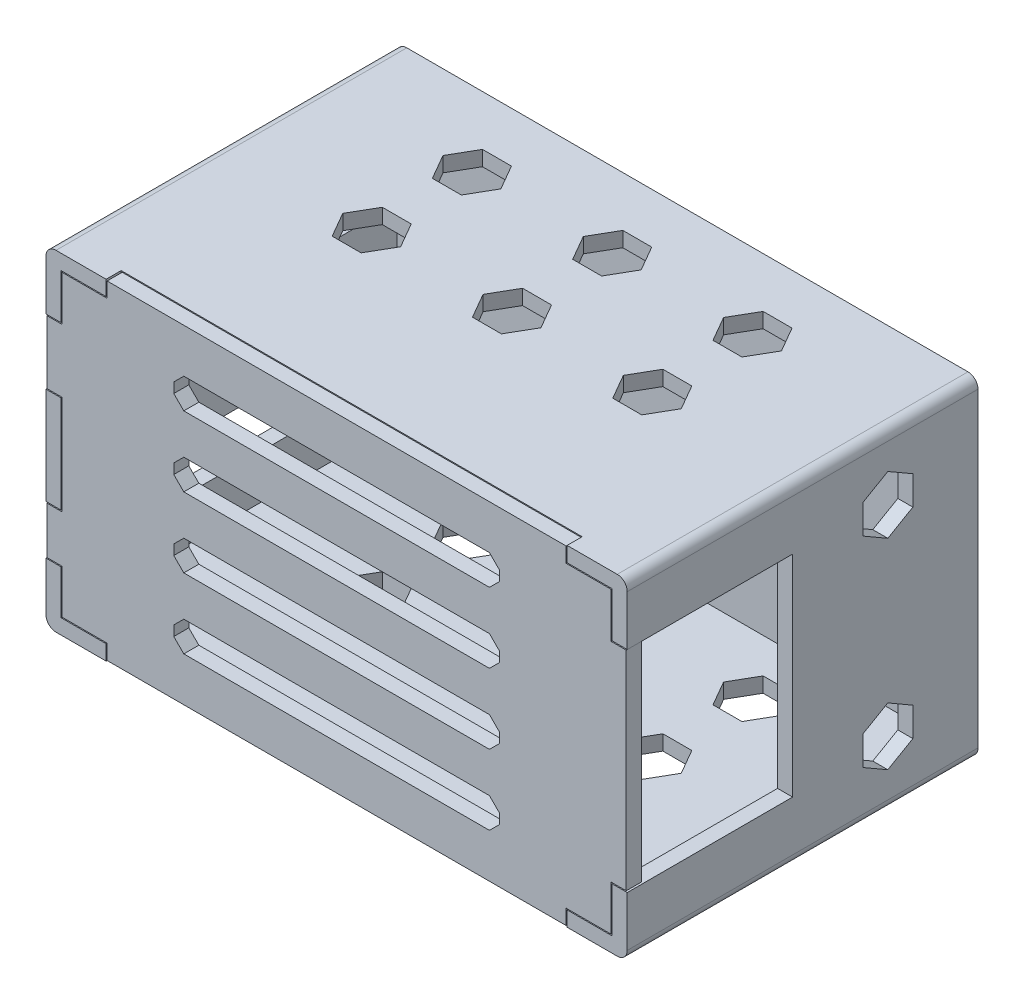
SolidWorks part; units mm, degrees
ref_plane "Front Plane" through (0, 0, 0) normal (0, 0, 1) x (1, 0, 0)
ref_plane "Top Plane" through (0, 0, 0) normal (0, 1, 0) x (1, 0, 0)
ref_plane "Right Plane" through (0, 0, 0) normal (1, 0, 0) x (0, 0, -1)
sketch "Sketch1" plane through (0, 0, 0) normal (0, 0, 1) x (1, 0, 0)
  line L0 (-58, -33) -> (-58, 33)
  line L1 (-55, -30) -> (55, -30)
  line L2 (-55, -30) -> (-55, 30)
  line L3 (-55, 30) -> (55, 30)
  line L4 (55, -30) -> (55, 30)
  line L5 (-55, -30) -> (55, 30) construction
  line L6 (-55, 30) -> (55, -30) construction
  line L7 (-58, 33) -> (58, 33)
  line L8 (58, -33) -> (58, 33)
  line L9 (-58, -33) -> (58, -33)
  point P0 (0, 0)
  dimension "D1" = 60
  dimension "125" = 110
  dimension "D3" = 3
extrude "Boss-Extrude1" add sketch "Sketch1" along normal blind 70
extrude "Boss-Extrude2" add sketch "Sketch1<2>" along normal blind 3 contours L1 L4 L3 L2 region at (0, 0, 0)
sketch "Sketch1<2>" plane through (0, 0, 0) normal (0, 0, 1) x (1, 0, 0) same geometry as "Sketch1"
sketch "Sketch2" plane through (-58, 0, 0) normal (-1, 0, 0) x (0, 0, 1)
  line L0 (70, 33) -> (70, -33) construction
  line L1 (70, -11.4) -> (5, -11.4)
  line L2 (70, -11.4) -> (70, -21.2)
  line L3 (70, -21.2) -> (5, -21.2)
  line L4 (5, -11.4) -> (5, -21.2)
  line L5 (0, 33) -> (0, -33) construction
  line L6 (70, 21) -> (5, 21)
  line L7 (70, 21) -> (70, 8)
  line L8 (70, 8) -> (5, 8)
  line L9 (5, 21) -> (5, 8)
  line L11 (70, 33) -> (0, 33) construction
  dimension "D1" = 5
  dimension "D2" = 13
  dimension "D3" = 9.8
  dimension "D4" = 19.4
  dimension "D5" = 12
extrude "Cut-Extrude1" cut sketch "Sketch2" against normal up to next
sketch "Sketch3" plane through (0, -33, 0) normal (0, -1, 0) x (1, 0, 0)
  line L0 (-58, 35) -> (58, 35) construction
  line L1 (-58, 70) -> (-58, 0) construction
  line L2 (58, 70) -> (58, 0) construction
  line L3 (-58, 15) -> (58, 15) construction
  line L9 (-25.1132, 40) -> (-30.8868, 40)
  line L14 (-30.8868, 40) -> (-33.7735, 35)
  line L15 (-33.7735, 35) -> (-30.8868, 30)
  line L20 (-30.8868, 30) -> (-25.1132, 30)
  line L21 (-25.1132, 30) -> (-22.2265, 35)
  line L22 (-58, 0) -> (58, 0) construction
  line L27 (-22.2265, 35) -> (-25.1132, 40)
  line L28 (2.8868, 40) -> (-2.8868, 40)
  line L33 (-2.8868, 40) -> (-5.7735, 35)
  line L34 (-5.7735, 35) -> (-2.8868, 30)
  line L39 (-2.8868, 30) -> (2.8868, 30)
  line L40 (2.8868, 30) -> (5.7735, 35)
  line L41 (5.7735, 35) -> (2.8868, 40)
  line L42 (30.8868, 40) -> (25.1132, 40)
  line L43 (25.1132, 40) -> (22.2265, 35)
  line L44 (22.2265, 35) -> (25.1132, 30)
  line L45 (25.1132, 30) -> (30.8868, 30)
  line L46 (30.8868, 30) -> (33.7735, 35)
  line L47 (33.7735, 35) -> (30.8868, 40)
  line L48 (30.8868, 20) -> (25.1132, 20)
  line L49 (25.1132, 20) -> (22.2265, 15)
  line L50 (22.2265, 15) -> (25.1132, 10)
  line L51 (25.1132, 10) -> (30.8868, 10)
  line L52 (30.8868, 10) -> (33.7735, 15)
  line L53 (33.7735, 15) -> (30.8868, 20)
  line L54 (2.8868, 20) -> (-2.8868, 20)
  line L55 (-2.8868, 20) -> (-5.7735, 15)
  line L56 (-5.7735, 15) -> (-2.8868, 10)
  line L57 (-2.8868, 10) -> (2.8868, 10)
  line L58 (2.8868, 10) -> (5.7735, 15)
  line L59 (5.7735, 15) -> (2.8868, 20)
  line L60 (-25.1132, 20) -> (-30.8868, 20)
  line L61 (-30.8868, 20) -> (-33.7735, 15)
  line L62 (-33.7735, 15) -> (-30.8868, 10)
  line L63 (-30.8868, 10) -> (-25.1132, 10)
  line L64 (-25.1132, 10) -> (-22.2265, 15)
  line L65 (-22.2265, 15) -> (-25.1132, 20)
  circle A0 centre (-28, 35) radius 5 construction
  circle A1 centre (0, 35) radius 5 construction
  circle A2 centre (28, 35) radius 5 construction
  circle A3 centre (28, 15) radius 5 construction
  circle A4 centre (0, 15) radius 5 construction
  circle A5 centre (-28, 15) radius 5 construction
  point P6 (-28, 35)
  point P11 (0, 35)
  point P16 (28, 35)
  point P23 (-28, 15)
  point P28 (0, 15)
  point P33 (28, 15)
  dimension "D5" = 10
  dimension "D1" = 28
  dimension "D2" = 28
  dimension "D3" = 15
  dimension "D4" = 20
extrude "Cut-Extrude2" cut sketch "Sketch3" against normal through all
sketch "Sketch4" plane through (58, 0, 0) normal (1, 0, 0) x (0, 0, -1)
  line L0 (-35, 33) -> (-35, -33) construction
  line L1 (-70, 33) -> (0, 33) construction
  line L2 (-40, -33) -> (-30, -33) construction
  line L3 (-18, 33) -> (-18, -33) construction
  line L4 (-20, -33) -> (-10, -33) construction
  line L5 (0, -33) -> (0, 33) construction
  line L7 (-40.7735, 20) -> (-37.8868, 15) construction
  line L8 (-37.8868, 15) -> (-32.1132, 15) construction
  line L9 (-32.1132, 15) -> (-29.2265, 20) construction
  line L10 (-29.2265, 20) -> (-32.1132, 25) construction
  line L11 (-32.1132, 25) -> (-37.8868, 25) construction
  line L12 (-37.8868, 25) -> (-40.7735, 20) construction
  line L13 (-18, 25.7735) -> (-23, 22.8868)
  line L14 (-23, 22.8868) -> (-23, 17.1132)
  line L15 (-23, 17.1132) -> (-18, 14.2265)
  line L16 (-18, 14.2265) -> (-13, 17.1132)
  line L17 (-13, 17.1132) -> (-13, 22.8868)
  line L18 (-13, 22.8868) -> (-18, 25.7735)
  line L19 (-18, -14.2265) -> (-23, -17.1132)
  line L20 (-23, -17.1132) -> (-23, -22.8868)
  line L21 (-23, -22.8868) -> (-18, -25.7735)
  line L22 (-18, -25.7735) -> (-13, -22.8868)
  line L23 (-13, -22.8868) -> (-13, -17.1132)
  line L24 (-13, -17.1132) -> (-18, -14.2265)
  line L25 (-40.7735, -20) -> (-37.8868, -25) construction
  line L26 (-37.8868, -25) -> (-32.1132, -25) construction
  line L27 (-32.1132, -25) -> (-29.2265, -20) construction
  line L28 (-29.2265, -20) -> (-32.1132, -15) construction
  line L29 (-32.1132, -15) -> (-37.8868, -15) construction
  line L30 (-37.8868, -15) -> (-40.7735, -20) construction
  circle A0 centre (-35, 20) radius 5 construction
  circle A1 centre (-18, 20) radius 5 construction
  circle A2 centre (-18, -20) radius 5 construction
  circle A3 centre (-35, -20) radius 5 construction
  dimension "D3" = 10
  dimension "D1" = 18
  dimension "D2" = 35
  dimension "D4" = 20
  dimension "D5" = 20
extrude "Cut-Extrude3" cut sketch "Sketch4" against normal up to next
sketch "Sketch5" plane through (0, 0, 70) normal (0, 0, 1) x (1, 0, 0)
  line L0 (58, 33) -> (-58, 33) construction
  line L1 (-46, 33) -> (46, 33)
  line L2 (-46, 33) -> (-46, 30)
  line L3 (-46, 30) -> (46, 30)
  line L4 (46, 33) -> (46, 30)
  line L5 (-55, 30) -> (55, 30) construction
  line L6 (58, -33) -> (58, 33) construction
  line L7 (-58, 33) -> (-58, 21) construction
  line L8 (-55, -30) -> (55, -30) construction
  line L9 (-46, -30) -> (46, -30)
  line L10 (-46, -30) -> (-46, -33)
  line L11 (-46, -33) -> (46, -33)
  line L12 (46, -30) -> (46, -33)
  line L13 (-58, -33) -> (58, -33) construction
  line L14 (-58, -21.2) -> (-58, -33) construction
  line L15 (55, -30) -> (55, 30) construction
  line L16 (55, 21) -> (58, 21)
  line L17 (55, 21) -> (55, -21)
  line L18 (55, -21) -> (58, -21)
  line L19 (58, 21) -> (58, -21)
  point P28 (55, 0)
  dimension "D1" = 12
  dimension "D2" = 12
  dimension "D3" = 12
  dimension "D4" = 12
  dimension "D5" = 12
extrude "Cut-Extrude4" cut sketch "Sketch5" against normal blind 3
sketch "Sketch6" plane through (0, 0, 67) normal (0, 0, 1) x (1, 0, 0)
  line L0 (-55, 21) -> (-58, 21) construction
  line L1 (-58, 21) -> (-58, 8) construction
  line L2 (-58, 8) -> (-55, 8) construction
  line L4 (-55, -11.4) -> (-58, -11.4) construction
  line L5 (-58, -11.4) -> (-58, -21.2) construction
  line L6 (-58, -21.2) -> (-55, -21.2) construction
  line L8 (-46, -30) -> (-46, -33) construction
  line L9 (-46, -33) -> (46, -33) construction
  line L10 (46, -33) -> (46, -30) construction
  line L13 (55, -21) -> (58, -21) construction
  line L14 (58, -21) -> (58, 21) construction
  line L15 (58, 21) -> (55, 21) construction
  line L16 (-46, 33) -> (-46, 30) construction
  line L18 (46, 30) -> (46, 33) construction
  line L19 (46, 33) -> (-46, 33) construction
  line L20 (-55, -30) -> (55, -30) construction
  line L21 (55, -30) -> (55, 30) construction
  line L22 (55, 30) -> (-55, 30) construction
  line L23 (-55, 30) -> (-55, -30) construction
  line L24 (-55, 21) -> (-58, 21)
  line L25 (-58, 21) -> (-58, 8)
  line L26 (-58, 8) -> (-55, 8)
  line L28 (-55, -11.4) -> (-58, -11.4)
  line L29 (-58, -11.4) -> (-58, -21.2)
  line L30 (-58, -21.2) -> (-55, -21.2)
  line L32 (-46, -30) -> (-46, -33)
  line L33 (-46, -33) -> (46, -33)
  line L34 (46, -33) -> (46, -30)
  line L37 (55, -21) -> (58, -21)
  line L38 (58, -21) -> (58, 21)
  line L39 (58, 21) -> (55, 21)
  line L40 (-46, 33) -> (-46, 30)
  line L42 (46, 30) -> (46, 33)
  line L43 (46, 33) -> (-46, 33)
  line L44 (-55, -30) -> (-46, -30)
  line L45 (55, -30) -> (55, -21)
  line L46 (55, 30) -> (46, 30)
  line L47 (-55, 30) -> (-55, 21)
  line L48 (-55, 8) -> (-55, -11.4)
  line L49 (-55, -21.2) -> (-55, -30)
  line L50 (46, -30) -> (55, -30)
  line L51 (55, 21) -> (55, 30)
  line L52 (-46, 30) -> (-55, 30)
  line L53 (54.8, 29.8) -> (45.8, 29.8)
  line L54 (45.8, 29.8) -> (45.8, 32.8)
  line L55 (45.8, 32.8) -> (-45.8, 32.8)
  line L56 (-45.8, 32.8) -> (-45.8, 29.8)
  line L57 (-45.8, 29.8) -> (-54.8, 29.8)
  line L58 (-54.8, 29.8) -> (-54.8, 20.8)
  line L59 (-54.8, 20.8) -> (-57.8, 20.8)
  line L60 (-57.8, 20.8) -> (-57.8, 8.2)
  line L61 (-57.8, 8.2) -> (-54.8, 8.2)
  line L62 (-54.8, 8.2) -> (-54.8, -11.6)
  line L63 (-54.8, -11.6) -> (-57.8, -11.6)
  line L64 (-57.8, -11.6) -> (-57.8, -21)
  line L65 (-57.8, -21) -> (-54.8, -21)
  line L66 (-54.8, -21) -> (-54.8, -29.8)
  line L67 (-54.8, -29.8) -> (-45.8, -29.8)
  line L68 (-45.8, -29.8) -> (-45.8, -32.8)
  line L69 (-45.8, -32.8) -> (45.8, -32.8)
  line L70 (45.8, -32.8) -> (45.8, -29.8)
  line L71 (45.8, -29.8) -> (54.8, -29.8)
  line L72 (54.8, -29.8) -> (54.8, -20.8)
  line L73 (54.8, -20.8) -> (57.8, -20.8)
  line L74 (57.8, -20.8) -> (57.8, 20.8)
  line L75 (57.8, 20.8) -> (54.8, 20.8)
  line L76 (54.8, 20.8) -> (54.8, 29.8)
  line M51 (55, 21) -> (55, -21)
  dimension "D1" = 0.2
extrude "Boss-Extrude3" add sketch "Sketch6" along normal blind 3 separate body contours L75 L76 L53 L54 L55 L56 L57 L58 L59 L60 L61 L62 L63 L64 L65 L66 L67 L68 L69 L70 L71 L72 L73 M51 | L74 L75 L73 M51 region at (-0.4554, 0.0124, 67) region at (56.4, 0, 67)
sketch "Sketch7" plane through (0, 0, 70) normal (0, 0, 1) x (1, 0, 0)
  line L1 (-32.5, 24) -> (32.5, 24)
  line L2 (-32.5, 24) -> (-32.5, 18)
  line L3 (-32.5, 18) -> (32.5, 18)
  line L4 (32.5, 24) -> (32.5, 18)
  line L5 (-32.5, 10) -> (32.5, 10)
  line L6 (-32.5, 10) -> (-32.5, 4)
  line L7 (-32.5, 4) -> (32.5, 4)
  line L8 (32.5, 10) -> (32.5, 4)
  line L9 (-32.5, -4) -> (32.5, -4)
  line L10 (-32.5, -4) -> (-32.5, -10)
  line L11 (-32.5, -10) -> (32.5, -10)
  line L12 (32.5, -4) -> (32.5, -10)
  line L13 (-32.5, -18) -> (32.5, -18)
  line L14 (-32.5, -18) -> (-32.5, -24)
  line L15 (-32.5, -24) -> (32.5, -24)
  line L16 (32.5, -18) -> (32.5, -24)
  point P16 (0, -18)
  point P17 (0, -4)
  point P19 (0, 10)
  point P20 (0, 24)
  dimension "D1" = 6
  dimension "D2" = 65
  dimension "D3" = 4
  dimension "D4" = 4
  dimension "D5" = 8
  dimension "D6" = 8
extrude "Cut-Extrude5" cut sketch "Sketch7" against normal up to next (3 mm away)
sketch "Sketch8" plane through (0, 0, 67) normal (0, 0, 1) x (1, 0, 0)
  line L4 (55, 21) -> (55, -21)
  line L5 (55, -21) -> (58, -21)
  line L6 (58, -21) -> (58, 21)
  line L7 (58, 21) -> (55, 21)
  line L8 (55, 21) -> (55, -21)
  line L9 (55, -21) -> (58, -21)
  line L10 (58, -21) -> (58, 21)
  line L11 (58, 21) -> (55, 21)
  dimension "D1" = 0
extrude "Cut-Extrude6" cut sketch "Sketch8" against normal blind 30
chamfer "Chamfer1" distance 2 angle 45 16 edges at (-32.5, 18, 68.5) (32.5, 18, 68.5) (32.5, 24, 68.5) (-32.5, 24, 68.5) (-32.5, 10, 68.5) (32.5, 10, 68.5) (32.5, 4, 68.5) (-32.5, 4, 68.5) (32.5, -4, 68.5) (-32.5, -4, 68.5) (-32.5, -10, 68.5) (32.5, -10, 68.5) (-32.5, -24, 68.5) (-32.5, -18, 68.5) (32.5, -24, 68.5) (32.5, -18, 68.5)
fillet "Fillet1" radius 2 4 edges at (58, 33, 35) (-58, 33, 35) (58, -33, 35) (-58, -33, 35)
